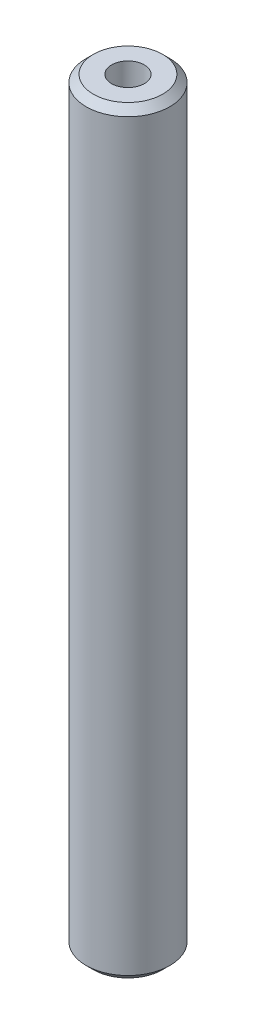
SolidWorks part; units mm, degrees
ref_plane "Front Plane" through (0, 0, 0) normal (0, 0, 1) x (1, 0, 0)
ref_plane "Top Plane" through (0, 0, 0) normal (0, 1, 0) x (1, 0, 0)
ref_plane "Right Plane" through (0, 0, 0) normal (1, 0, 0) x (0, 0, -1)
sketch "Sketch1" plane through (0, 0, 0) normal (0, 1, 0) x (1, 0, 0)
  circle A0 centre (0, 0) radius 12.5
  dimension "SHAFT_OD" = 25
extrude "Boss-Extrude1" add sketch "Sketch1" along normal blind 226.5201
sketch "Sketch2" plane through (0, 0, 0) normal (0, 1, 0) x (1, 0, 0)
  circle A0 centre (0, 0) radius 4.8854
  dimension "BORE_D" = 9.7708
extrude "Cut-Extrude1" cut sketch "Sketch2" along normal through all
chamfer "Chamfer1" distance 2.1586 angle 45 2 edges at (0, 226.5201, 12.5) (0, 0, 12.5)
